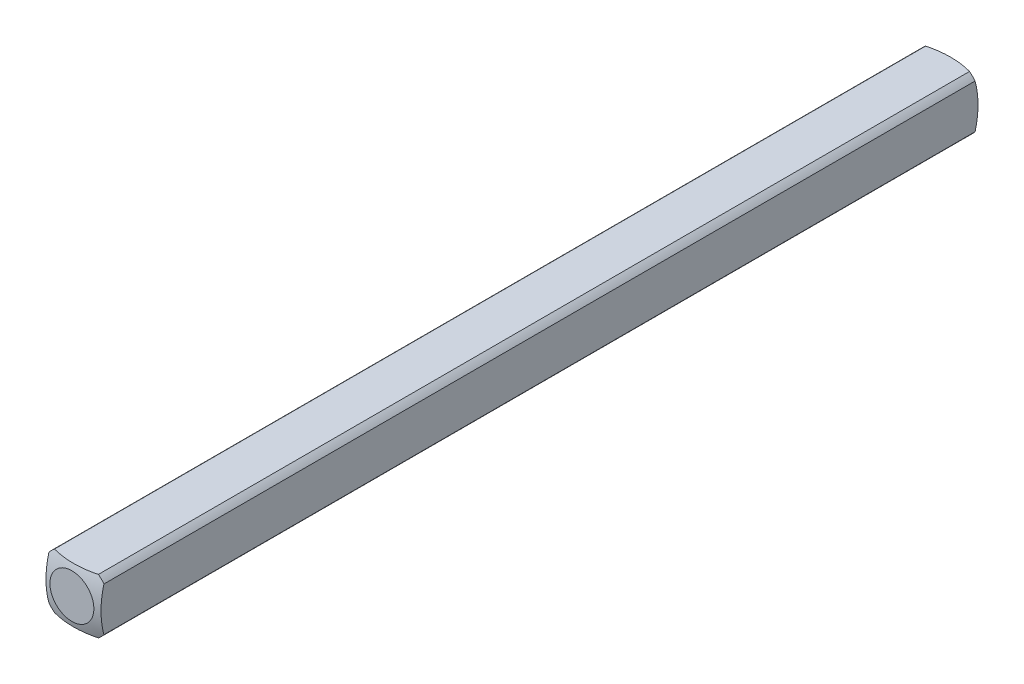
SolidWorks part; units mm, degrees
material "Custom Plastic"
ref_plane "Front Plane" through (0, 0, 0) normal (0, 0, 1) x (1, 0, 0)
ref_plane "Top Plane" through (0, 0, 0) normal (0, 1, 0) x (1, 0, 0)
ref_plane "Right Plane" through (0, 0, 0) normal (1, 0, 0) x (0, 0, -1)
sketch "Sketch1" plane through (0, 0, 0) normal (0, 0, 1) x (1, 0, 0)
  line L0 (-1.5875, -1.5875) -> (1.5875, 1.5875) construction
  line L1 (-1.5875, -1.5875) -> (1.5875, -1.5875)
  line L2 (-1.5875, -1.5875) -> (-1.5875, 1.5875)
  line L3 (-1.5875, 1.5875) -> (1.5875, 1.5875)
  line L4 (1.5875, -1.5875) -> (1.5875, 1.5875)
  dimension "D1" = 3.175
extrude "Boss-Extrude1" add sketch "Sketch1" along normal blind 25.4
sketch "Sketch2" plane through (0, 0, 0) normal (0, 0, -1) x (-1, 0, 0)
  circle A0 centre (0, 0) radius 2.032
  dimension "D1" = 4.064
extrude "Cut-Extrude1" cut sketch "Sketch2" against normal through all flip side to cut
ref_axis "Axis1" through (0, 0, 25.4) along (0, 0, -1)
sketch "Sketch3" plane through (0, 0, 0) normal (0, 1, 0) x (1, 0, 0)
  line L1 (-5.0537, -4.4027) -> (-5.0537, 5.7405)
  line L2 (-5.0537, 5.7405) -> (0, 5.7405)
  line L5 (0, -25.4) -> (0, 0) construction
  line L8 (0, 0.1609) -> (0, 5.7405)
  arc A0 (-5.0537, -4.4027) -> (0, 0.1609) centre (0, -4.9191) cw
  dimension "D1" = 5.08
revolve "Cut-Revolve1" cut sketch "Sketch3" angle 360 about axis through (0, 0, 25.4) along (0, 0, -1)
mirror "Mirror1" about plane through (0, 0, 25.4) normal (0, 0, -1) of bodies 103
